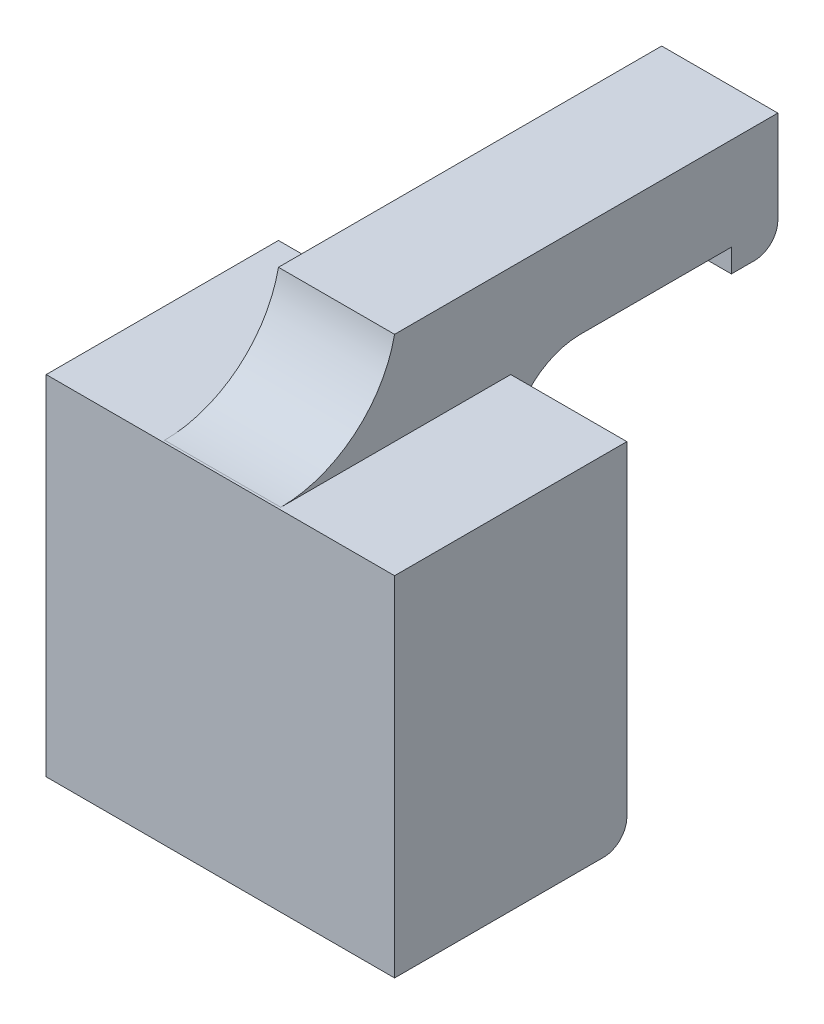
SolidWorks part; units mm, degrees
other "Markup1"
sketch "Sketch8" plane through (-7.5, -7.5, 10) normal (-0.045, -0.9988, 0.0171) x (0.0128, -0.0177, -0.9998)
ref_plane "Front Plane" through (0, 0, 0) normal (0, 0, 1) x (1, 0, 0)
ref_plane "Top Plane" through (0, 0, 0) normal (0, 1, 0) x (1, 0, 0)
ref_plane "Right Plane" through (0, 0, 0) normal (1, 0, 0) x (0, 0, -1)
sketch "Sketch1" plane through (0, 0, 0) normal (0, 0, 1) x (1, 0, 0)
  line L1 (-7.5, -7.5) -> (7.5, -7.5)
  line L2 (-7.5, -7.5) -> (-7.5, 7.5)
  line L3 (-7.5, 7.5) -> (7.5, 7.5)
  line L4 (7.5, -7.5) -> (7.5, 7.5)
  line L5 (-7.5, -7.5) -> (7.5, 7.5) construction
  line L6 (-7.5, 7.5) -> (7.5, -7.5) construction
  point P0 (0, 0)
  dimension "D1" = 15
  dimension "D2" = 15
extrude "Boss-Extrude1" add sketch "Sketch1" along normal blind 10
sketch "Sketch2" plane through (0, 0, 0) normal (0, 0, -1) x (-1, 0, 0)
  circle A0 centre (0, 0) radius 2.75
  dimension "D1" = 5.5
extrude "Boss-Extrude2" add sketch "Sketch2" along normal blind 3
sketch "Sketch3" plane through (0, 7.5, 0) normal (0, 1, 0) x (1, 0, 0)
  line L0 (0, 0) -> (0, -10)
  line L1 (7.5, -10) -> (-7.5, -10) construction
  line L2 (0, -5) -> (-2.5, -5)
  line L3 (0, -5) -> (2.5, -5)
  line L4 (-2.5, -5) -> (-2.5, 11.5)
  line L5 (-2.5, 11.5) -> (2.5, 11.5)
  line L6 (2.5, 11.5) -> (2.5, -5)
  line M4 (7.5, 0) -> (-7.5, 0)
  dimension "D1" = 2.5
  dimension "D2" = 2.5
  dimension "D3" = 16.5
extrude "Boss-Extrude3" add sketch "Sketch3" along normal blind 4 contours L6 L5 L4 M4 | L6 L0 L3 M4 | L4 L2 L0 M4 region at (1.25, 7.5, 2.5) region at (0, 7.5, -5.75) region at (-1.25, 7.5, 2.5)
fillet "Fillet1" radius 5 1 edges at (0, 7.5, 5)
fillet "Fillet2" radius 3 1 edges at (0, 7.5, 0)
sketch "Sketch4" plane through (0, 7.5, 0) normal (0, -1, 0) x (1, 0, 0)
  line L0 (2.5, -11.5) -> (2.5, -3) construction
  line L1 (-2.5, -11.5) -> (2.5, -11.5)
  line L2 (-2.5, -11.5) -> (-2.5, -9.5)
  line L3 (-2.5, -9.5) -> (2.5, -9.5)
  line L4 (2.5, -11.5) -> (2.5, -9.5)
  dimension "D1" = 2
extrude "Boss-Extrude4" add sketch "Sketch4" along normal blind 1
fillet "Fillet3" radius 1 1 edges at (0, 6.5, -11.5)
sketch "Sketch5" plane through (0, -7.5, 0) normal (0, -1, 0) x (1, 0, 0)
  line L0 (0, 0) -> (0, 10)
  line L1 (-7.5, 10) -> (7.5, 10) construction
  line L3 (-2.75, 8.8385) -> (2.75, 8.8385)
  line L4 (-2.75, 8.8385) -> (-2.75, 1.1615)
  line L5 (-2.75, 1.1615) -> (2.75, 1.1615)
  line L6 (2.75, 8.8385) -> (2.75, 1.1615)
  line L7 (-2.75, 8.8385) -> (2.75, 1.1615) construction
  line L8 (-2.75, 1.1615) -> (2.75, 8.8385) construction
  point P5 (0, 5)
  dimension "D1" = 5.5
extrude "Cut-Extrude1" cut sketch "Sketch5" against normal blind 1 contours L4 L5 L0 L3 | L6 L3 L0 L5 region at (-1.375, -7.5, 5) region at (1.375, -7.5, 5)
sketch "Sketch6" plane through (0, 0, 0) normal (0, 0, -1) x (-1, 0, 0)
  line L0 (0, 0) -> (-5, 0)
  circle A0 centre (-5, 0) radius 1
  dimension "D2" = 2
  dimension "D1" = 5
extrude "Cut-Extrude2" cut sketch "Sketch6" against normal blind 8 contours A0 region at (5.9717, 0, 0)
sketch "Sketch7" plane through (0, 0, 0) normal (0, 0, -1) x (-1, 0, 0)
  line L0 (0, 0) -> (5, 0)
  circle A0 centre (5, 0) radius 0.875
  dimension "D2" = 1.75
  dimension "D1" = 5
extrude "Boss-Extrude5" add sketch "Sketch7" along normal blind 7.5 contours A0 region at (-5, -0.8503, 0)
fillet "Fillet5" radius 1 1 edges at (0, -7.5, 0)
